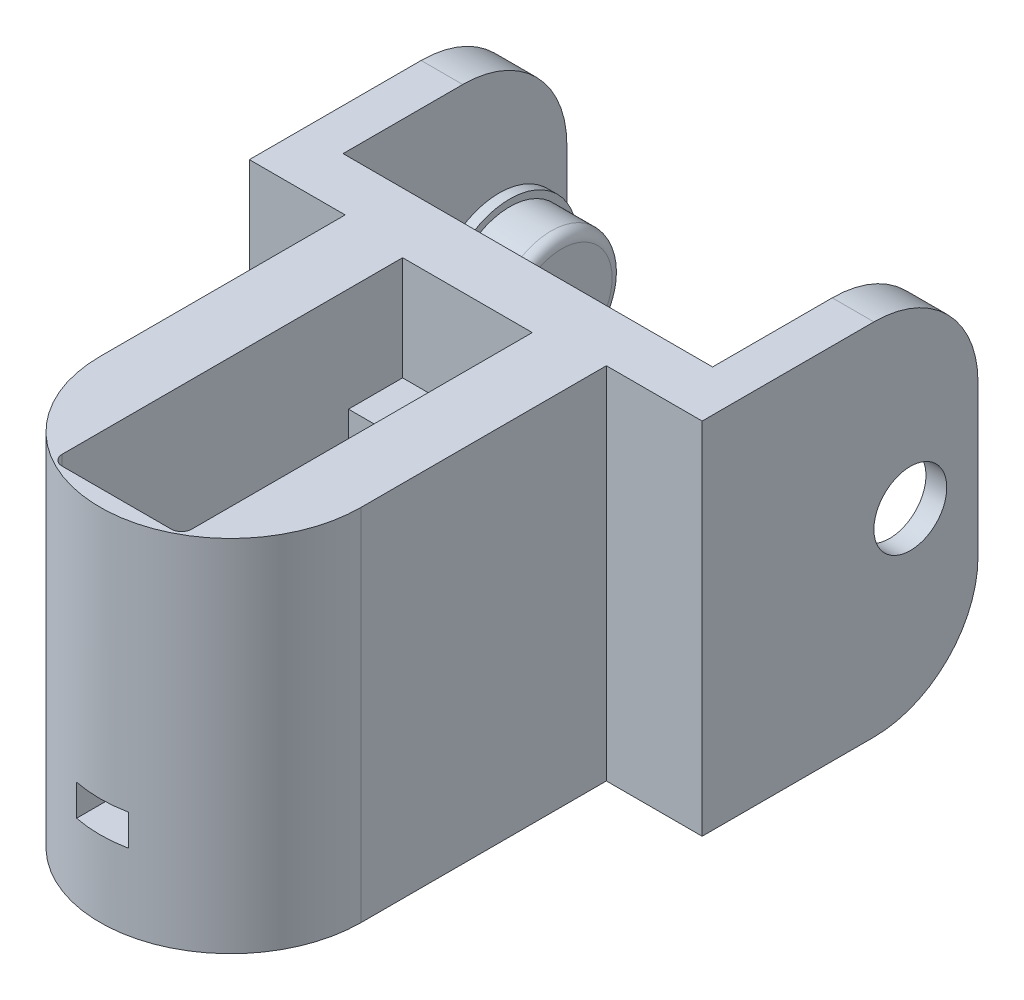
SolidWorks part; units mm, degrees
ref_plane "Front Plane" through (0, 0, 0) normal (0, 0, 1) x (1, 0, 0)
ref_plane "Top Plane" through (0, 0, 0) normal (0, 1, 0) x (1, 0, 0)
ref_plane "Right Plane" through (0, 0, 0) normal (1, 0, 0) x (0, 0, -1)
sketch "Sketch4" plane through (0, 0, 0) normal (0, 0, 1) x (1, 0, 0)
  line L1 (-6.23, -9.975) -> (6.23, -9.975)
  line L2 (-6.23, -9.975) -> (-6.23, 7.275)
  line L3 (-6.23, 7.275) -> (6.23, 7.275)
  line L4 (6.23, -9.975) -> (6.23, 7.275)
  point P4 (0, 7.275)
  dimension "D1" = 12.46
  dimension "D2" = 17.25
  dimension "D3" = 9.975
extrude "Boss-Extrude3" add sketch "Sketch4" along normal blind 6
sketch "Sketch8" plane through (0, -9.975, 0) normal (0, -1, 0) x (-1, 0, 0)
  circle A0 centre (0, -23.55) radius 12.5468
  circle A1 centre (0, -23.55) radius 11.15
  dimension "D1" = 22.3
  dimension "D2" = 23.55
extrude "Boss-Extrude6" add sketch "Sketch8" along normal blind 7.3 and the other way up to surface (17.25 mm away) other way up to face at (0, 7.275, 3)
sketch "Sketch5" plane through (0, 7.275, 0) normal (0, 1, 0) x (1, 0, 0)
  line L8 (12.5468, -23.55) -> (12.5468, 0)
  line L9 (12.5468, 0) -> (6.23, 0)
  line L10 (-12.5468, -23.55) -> (-12.5468, 0)
  line L11 (-12.5468, 0) -> (-6.23, 0)
  line L12 (-6.23, 0) -> (-6.23, -29.7)
  line L14 (6.23, -29.7) -> (6.23, 0)
  line L15 (-6.23, -29.7) -> (6.23, -29.7)
  line L16 (6.23, -6) -> (-6.23, -6) construction
  circle A0 centre (0, -23.55) radius 12.5468 construction
  arc A1 (-12.5468, -23.55) -> (12.5468, -23.55) centre (0, -23.55) ccw
  dimension "D1" = 23.7
  dimension "D2" = 23.55
extrude "Boss-Extrude4" add sketch "Sketch5" against normal up to surface (17.25 mm away) up to face at (0, -9.975, 3)
sketch "Sketch6" plane through (0, 7.275, 0) normal (0, 1, 0) x (1, 0, 0)
  line L0 (6.23, -6) -> (-6.23, -6) construction
  line L3 (6.23, -29.7) -> (-6.23, -29.7) construction
  circle A0 centre (0, -3.6) radius 0.5
  circle A1 centre (0, -32.1) radius 0.5
  dimension "D1" = 1
  dimension "D3" = 1
  dimension "D2" = 2.4
  dimension "D4" = 2.4
extrude "Cut-Extrude1" cut sketch "Sketch6" against normal blind 5
chamfer "Chamfer1" distance 0.5 angle 60 2 edges at (0, 7.275, 4.1) (0, 7.275, 32.6) first distance on face at (0, 7.275, 4.1)
sketch "Sketch10" plane through (0, 7.275, 0) normal (0, 1, 0) x (1, 0, 0)
  line L1 (-6.23, -6) -> (6.23, -6)
  line L2 (-6.23, -6) -> (-6.23, -29.7)
  line L3 (-6.23, -29.7) -> (6.23, -29.7)
  line L4 (6.23, -6) -> (6.23, -29.7)
extrude "Cut-Extrude3" cut sketch "Sketch10" against normal up to surface (17.25 mm away) up to face at (0, -9.975, 27.1007)
ref_plane "Plane1" through (0, 0, 36.0968) normal (0, 0, 1) x (1, 0, 0)
sketch "Sketch11" plane through (0, 0, 36.0968) normal (0, 0, 1) x (1, 0, 0)
  line L0 (-11.15, -9.975) -> (11.15, -9.975) construction
  line L1 (-2.5, -6.975) -> (2.5, -6.975)
  line L2 (-2.5, -6.975) -> (-2.5, -9.975)
  line L3 (-2.5, -9.975) -> (2.5, -9.975)
  line L4 (2.5, -6.975) -> (2.5, -9.975)
  point P4 (0, -6.975)
  dimension "D1" = 0
  dimension "D2" = 5
  dimension "D3" = 3
extrude "Cut-Extrude4" cut sketch "Sketch11" against normal up to next
sketch "Sketch13" plane through (0, -17.275, 0) normal (0, -1, 0) x (1, 0, 0)
  line L0 (-12.5468, 23.55) -> (-12.5468, 0)
  line L1 (-12.5468, 0) -> (12.5468, 0)
  line L2 (12.5468, 0) -> (12.5468, 23.55)
  arc A0 (-12.5468, 23.55) -> (12.5468, 23.55) centre (0, 23.55) ccw
  point P3 (0, 0)
extrude "Boss-Extrude7" add sketch "Sketch13" against normal up to surface (7.3 mm away) up to face at (6.0145, -9.975, 27.3356)
sketch "Sketch15" plane through (0, 7.275, 0) normal (0, 1, 0) x (1, 0, 0)
  line L0 (-12.5468, 0) -> (12.5468, 0)
  line L1 (12.5468, 0) -> (12.5468, -23.55)
  line L2 (-12.5468, 0) -> (-12.5468, -23.55)
  line L3 (6.23, -6) -> (6.23, -29.7) construction
  line L4 (-6.23, -0.8) -> (6.23, -0.8)
  line L5 (-6.23, -0.8) -> (-6.23, -33.5)
  line L6 (-5.23, -34.5) -> (5.23, -34.5)
  line L7 (6.23, -0.8) -> (6.23, -33.5)
  arc A0 (-12.5468, -23.55) -> (12.5468, -23.55) centre (0, -23.55) ccw
  circle A1 centre (0, -3.6) radius 0.5 construction
  arc A2 (5.23, -34.5) -> (6.23, -33.5) centre (5.23, -33.5) ccw
  arc A3 (-6.23, -33.5) -> (-5.23, -34.5) centre (-5.23, -33.5) ccw
  point P15 (0, -0.8)
  dimension "D1" = 0.8
  dimension "D3" = 1
  dimension "D2" = 2.8
  dimension "D4" = 0
  dimension "D5" = 34.5
extrude "Boss-Extrude9" add sketch "Sketch15" along normal blind 10
sketch "Sketch20" plane through (0, -17.275, 0) normal (0, -1, 0) x (1, 0, 0)
  circle A0 centre (0, 23.55) radius 7.15
  circle A1 centre (0, 23.55) radius 11.15
  circle A2 centre (0, 23.55) radius 11.15 construction
  dimension "D1" = 14.3
extrude "Boss-Extrude11" add sketch "Sketch20" against normal up to surface (7.3 mm away) up to face at (-6.0145, -9.975, 27.3356)
sketch "Sketch21" plane through (0, -17.275, 0) normal (0, -1, 0) x (1, 0, 0)
  circle A0 centre (0, 23.55) radius 7.15
  circle A1 centre (0, 23.55) radius 10.15
  circle A2 centre (0, 23.55) radius 7.15 construction
  dimension "D1" = 20.3
extrude "Cut-Extrude7" cut sketch "Sketch21" against normal blind 1.3
sketch "Sketch17" plane through (0, 17.275, 0) normal (0, 1, 0) x (1, 0, 0)
  line L0 (21.75, 26.5) -> (21.75, 0)
  line L1 (21.75, 0) -> (-21.75, 0)
  line L2 (-21.75, 0) -> (-21.75, 26.5)
  line L3 (-21.75, 26.5) -> (-17.75, 26.5)
  line L4 (-17.75, 26.5) -> (-17.75, 5)
  line L5 (-17.75, 5) -> (17.75, 5)
  line L6 (17.75, 5) -> (17.75, 26.5)
  line L7 (17.75, 26.5) -> (21.75, 26.5)
  point P2 (0, 5)
  point P10 (0, 0)
  dimension "D1" = 4
  dimension "D2" = 35.5
  dimension "D3" = 0
  dimension "D4" = 26.5
  dimension "D5" = 5
extrude "Boss-Extrude10" add sketch "Sketch17" against normal up to surface (34.55 mm away) up to face at (0, -17.275, 13.4)
sketch "Sketch18" plane through (17.75, 0, 0) normal (-1, 0, 0) x (0, 0, 1)
  line L0 (-26.5, -17.275) -> (-26.5, 17.275) construction
  line L1 (-26.5, 6.2191) -> (-5, 6.2191)
  line L2 (-26.5, 6.2191) -> (-26.5, -6.2191)
  line L3 (-26.5, -6.2191) -> (-5, -6.2191)
  line L4 (-5, 6.2191) -> (-5, -6.2191)
  line L5 (-5, -17.275) -> (-5, 17.275) construction
  point P6 (-26.5, 0)
  point P7 (-26.5, 0)
  dimension "D1" = 0
extrude "Cut-Extrude5" cut sketch "Sketch18" against normal blind 2
sketch "Sketch19" plane through (19.75, 0, 0) normal (-1, 0, 0) x (0, 0, 1)
  line L0 (-26.5, -17.275) -> (-26.5, 17.275) construction
  circle A0 centre (-20, 0) radius 3.5
  dimension "D1" = 7
  dimension "D2" = 6.5
extrude "Cut-Extrude6" cut sketch "Sketch19" against normal through all both and the other way through all
fillet "Fillet1" radius 10 4 edges at (19.75, -17.275, -26.5) (19.75, 17.275, -26.5) (-19.75, 17.275, -26.5) (-19.75, -17.275, -26.5)
ref_plane "Plane2" through (0, 0, 0) normal (1, 0, 0) x (0, 0, -1)
ref_plane "Plane3" through (0, 0, 0) normal (0, -1, 0) x (-1, 0, 0)
sketch "Sketch22" plane through (-21.75, 0, 0) normal (-1, 0, 0) x (0, 0, 1)
  circle A0 centre (-20, 0) radius 6.5
  dimension "D1" = 13
extrude "Boss-Extrude12" add sketch "Sketch22" against normal blind 5
sketch "Sketch23" plane through (-16.75, 0, 0) normal (1, 0, 0) x (0, 0, -1)
  circle A0 centre (20, 0) radius 5.85
  dimension "D1" = 11.7
extrude "Boss-Extrude13" add sketch "Sketch23" along normal blind 5
fillet "Fillet2" radius 1 1 edges at (-11.75, 0, -25.85)
